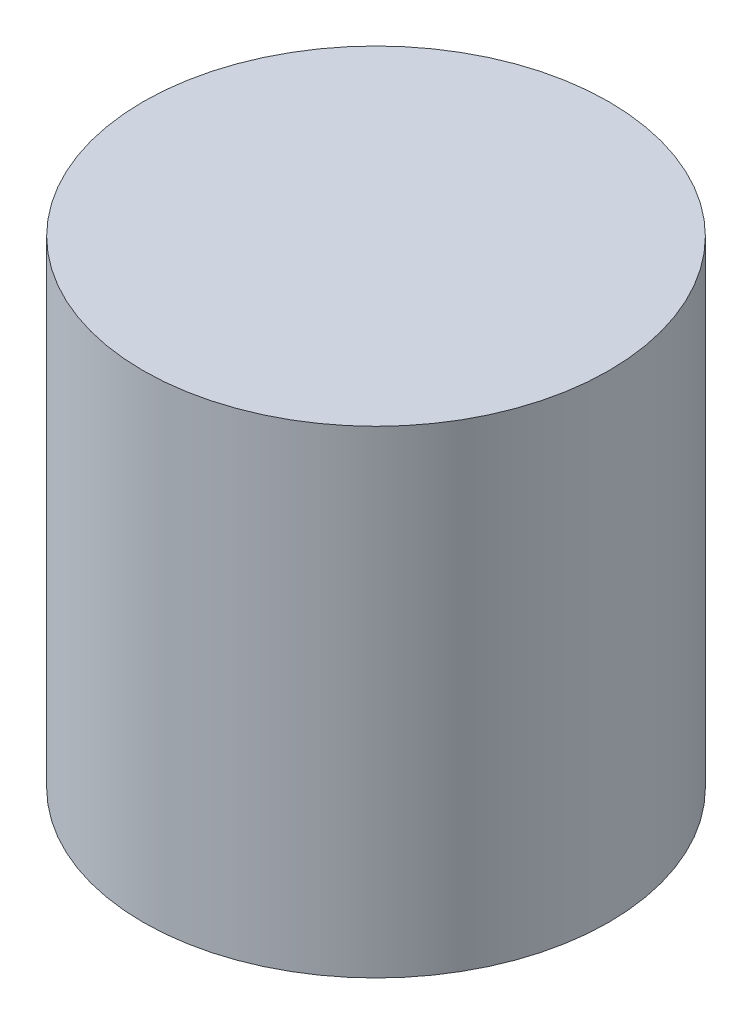
SolidWorks part; units mm, degrees
ref_plane "Alzado" through (0, 0, 0) normal (0, 0, 1) x (1, 0, 0)
ref_plane "Planta" through (0, 0, 0) normal (0, 1, 0) x (1, 0, 0)
ref_plane "Vista lateral" through (0, 0, 0) normal (1, 0, 0) x (0, 0, -1)
sketch "Sketch1" plane through (0, 0, 0) normal (0, 1, 0) x (1, 0, 0)
  circle A0 centre (0, 0) radius 19.5
  dimension "D1" = 39
extrude "Boss-Extrude1" add sketch "Sketch1" along normal blind 3
sketch "Sketch2" plane through (0, 0, 0) normal (0, -1, 0) x (-1, 0, 0)
  circle A0 centre (0, 0) radius 18
  circle A1 centre (0, 0) radius 19.5
  dimension "D1" = 36
  dimension "D2" = 39
extrude "Boss-Extrude2" add sketch "Sketch2" along normal blind 37
fillet "Fillet1" radius 5 1 edges at (0, -37, -18)
sketch "Sketch3" plane through (0, 3, 0) normal (0, 1, 0) x (1, 0, 0)
  circle A0 centre (0, 0) radius 18
  circle A1 centre (0, 0) radius 17.4
  circle A2 centre (0, 0) radius 17 construction
  dimension "D1" = 36
  dimension "D3" = 0.4
extrude "Boss-Extrude3" add sketch "Sketch3" against normal blind 6
